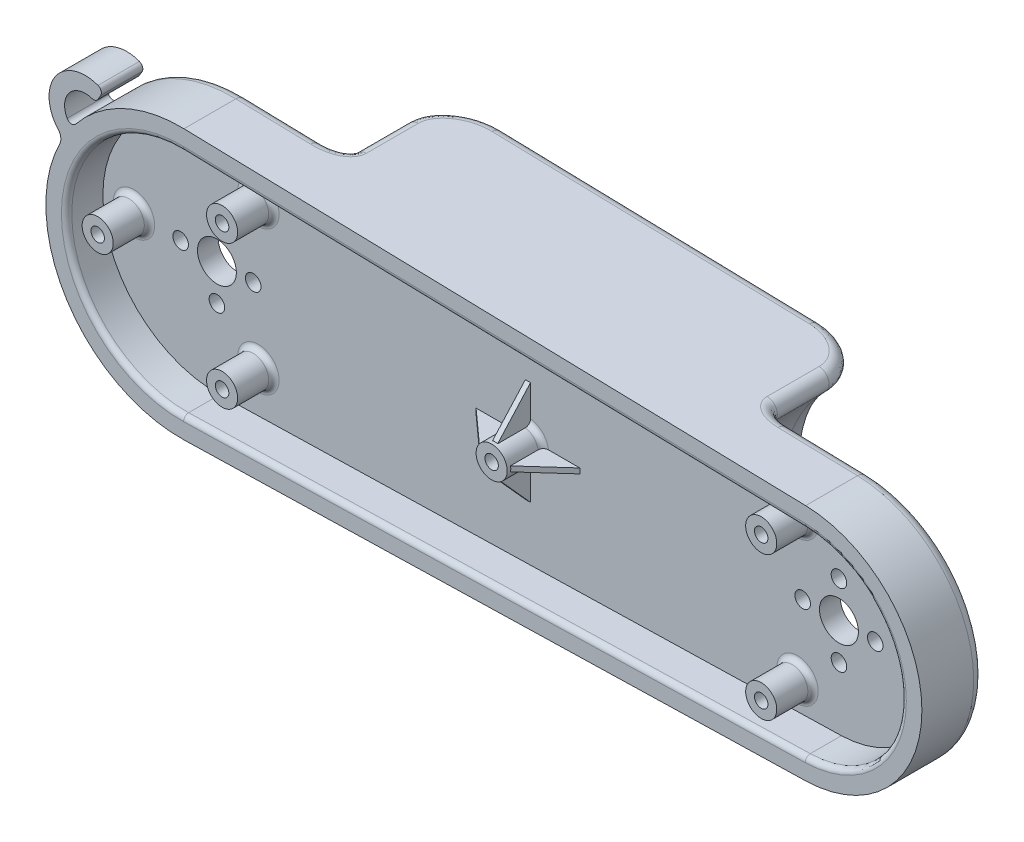
SolidWorks part; units mm, degrees
ref_plane "Front Plane" through (0, 0, 0) normal (0, 0, 1) x (1, 0, 0)
ref_plane "Top Plane" through (0, 0, 0) normal (0, 1, 0) x (1, 0, 0)
ref_plane "Right Plane" through (0, 0, 0) normal (1, 0, 0) x (0, 0, -1)
sketch "Sketch1" plane through (0, 0, 0) normal (0, 0, 1) x (1, 0, 0)
  line L2 (0.65, -25.9919) -> (120.575, -22.9928)
  line L3 (0.65, 25.9919) -> (120.575, 22.9928)
  circle A0 centre (0, 0) radius 3.75
  circle A1 centre (-7, 0) radius 1.5
  circle A2 centre (0, 7) radius 1.5
  circle A3 centre (0, -7) radius 1.5
  circle A4 centre (7, 0) radius 1.5
  arc A5 (0.65, 25.9919) -> (0.65, -25.9919) centre (0, 0) ccw
  circle A6 centre (120, 0) radius 3.75
  circle A7 centre (120, -7) radius 1.5
  circle A8 centre (113, 0) radius 1.5
  circle A9 centre (127, 0) radius 1.5
  circle A10 centre (120, 7) radius 1.5
  arc A11 (120.575, -22.9928) -> (120.575, 22.9928) centre (120, 0) ccw
extrude "Boss-Extrude1" add sketch "Sketch1" along normal blind 12
sketch "Sketch2" plane through (0, 0, 0) normal (0, 0, -1) x (-1, 0, 0)
  circle A0 centre (-120, 0) radius 11
  circle A1 centre (0, 0) radius 11
extrude "Cut-Extrude1" cut sketch "Sketch2" against normal blind 1
sketch "Sketch4" plane through (0, 0, 12) normal (0, 0, 1) x (1, 0, 0)
  line L4 (0.55, -21.9931) -> (120.475, -18.9941)
  line L5 (120.475, 18.9941) -> (0.55, 21.9931)
  line L6 (0.55, -21.9931) -> (120.475, -18.9941)
  line L7 (120.475, 18.9941) -> (0.55, 21.9931)
  arc A4 (0.55, 21.9931) -> (0.55, -21.9931) centre (0, 0) ccw
  arc A5 (120.475, -18.9941) -> (120.475, 18.9941) centre (120, 0) ccw
  arc A6 (0.55, 21.9931) -> (0.55, -21.9931) centre (0, 0) ccw
  arc A7 (120.475, -18.9941) -> (120.475, 18.9941) centre (120, 0) ccw
  dimension "D1" = 4
extrude "Cut-Extrude2" cut sketch "Sketch4" against normal blind 7
sketch "Sketch5" plane through (0, 0, 5) normal (0, 0, 1) x (1, 0, 0)
  line L0 (8, 13.8564) -> (0, 0) construction
  line L1 (-16, 0) -> (0, 0) construction
  line L2 (112, 13.8564) -> (120, 0) construction
  line L3 (120, 0) -> (112, -13.8564) construction
  circle A0 centre (-16, 0) radius 3
  circle A1 centre (8, 13.8564) radius 3
  circle A2 centre (8, -13.8564) radius 3
  circle A3 centre (60, 0) radius 3
  circle A4 centre (112, 13.8564) radius 3
  circle A5 centre (112, -13.8564) radius 3
  dimension "D1" = 6
  dimension "D2" = 16
  dimension "D3" = 60
  dimension "D4" = 120
  dimension "D5" = 120
extrude "Boss-Extrude2" add sketch "Sketch5" along normal up to surface (7 mm away) up to face at (59.5062, 0, 12)
sketch "Sketch6" plane through (0, 0, 12) normal (0, 0, 1) x (1, 0, 0)
  circle A0 centre (8, 13.8564) radius 1.3
  circle A1 centre (60, 0) radius 1.3
  circle A2 centre (-16, 0) radius 1.3
  circle A3 centre (8, -13.8564) radius 1.3
  circle A4 centre (112, -13.8564) radius 1.3
  circle A5 centre (112, 13.8564) radius 1.3
extrude "Cut-Extrude3" cut sketch "Sketch6" against normal blind 8
fillet "Fillet1" radius 1 6 edges at (115, 13.8564, 5) (115, -13.8564, 5) (63, 0, 5) (11, -13.8564, 5) (11, 13.8564, 5) (-13, 0, 5)
fillet "Fillet2" radius 1 4 edges at (139, 0, 12) (-22, 0, 12) (60.5125, -20.4936, 12) (60.5125, 20.4936, 12)
ref_plane "Plane1" through (0, 0, 8) normal (0, 0, -1) x (-1, 0, 0)
sketch "Sketch7" plane through (0, 0, 8) normal (0, 0, -1) x (-1, 0, 0)
  line L0 (0, 0) -> (43.0293, 43.0293) construction
sketch "Sketch9" plane through (0, 0, 0) normal (0, 0, -1) x (-1, 0, 0)
  line L0 (-104.6113, 23.392) -> (-15.612, 25.6177)
  line L1 (-120.575, 22.9928) -> (-0.65, 25.9919) construction
  line L2 (-87.8013, -23.8124) -> (-33.5373, -25.1694)
  line L3 (-33.5373, -25.1694) -> (-29.748, 3.8804)
  line L4 (-0.65, -25.9919) -> (-120.575, -22.9928) construction
  line L5 (-87.8013, -23.8124) -> (-92.3567, 4.4549)
  arc A0 (-92.3567, 4.4549) -> (-104.6113, 23.392) centre (-120, 0) ccw
  arc A1 (-15.612, 25.6177) -> (-29.748, 3.8804) centre (0, 0) ccw
extrude "Boss-Extrude3" add sketch "Sketch9" along normal blind 20
fillet "Fillet3" radius 10 2 edges at (33.5373, -25.1694, -10) (87.8013, -23.8124, -10)
fillet "Fillet4" radius 2 6 edges at (35.7852, -22.5438, 0) (31.0603, -6.1803, 0) (85.8287, -21.5543, 0) (90.7396, -5.5797, 0) (25.1497, 16.3552, 0) (96.4927, 15.212, 0)
fillet "Fillet5" radius 8 7 edges at (25.1497, 16.3552, -20) (31.0603, -6.1803, -20) (35.7852, -22.5438, -20) (61.0192, -24.4822, -20) (85.8287, -21.5543, -20) (90.7396, -5.5797, -20) (96.4927, 15.212, -20)
fillet "Fillet6" radius 2 15 edges at (83.2488, -23.9263, -0.4974) (103.353, -23.4235, 0) (38.7897, -25.0381, -0.4974) (18.2787, -25.551, 0) (-26, 0, 0) (5.8445, 25.862, 0) (15.3352, 25.6246, -1.2721) (15.612, 25.6177, -7) (18.0765, 25.5561, -16.376) (60.6215, 24.4921, -20) (103.296, 23.4249, -15.4259) (104.6113, 23.392, -7) (105.0798, 23.3803, -1.0058) (114.5147, 23.1444, 0) (143, 0, 0)
sketch "Sketch10" plane through (0, 0, 8) normal (0, 0, -1) x (-1, 0, 0)
  line L0 (0, 0) -> (43.0293, 43.0293) construction
  line L1 (16.3848, 21.8489) -> (14.8848, 24.447)
  line L2 (20.2627, 14.853) -> (21.6711, 12.2041)
  arc A0 (22.6232, 12.8138) -> (20.9873, 15.3472) centre (0, 0) ccw
  arc A1 (21.6711, 12.2041) -> (14.8848, 24.447) centre (18.3848, 18.3848) ccw
  arc A2 (20.2627, 14.853) -> (16.3848, 21.8489) centre (18.3848, 18.3848) ccw
  dimension "D1" = 52
  dimension "D2" = 14
  dimension "D3" = 8
  dimension "D4" = 75
  dimension "D5" = 107
extrude "Boss-Extrude4" add sketch "Sketch10" along normal mid plane 8 contours A2 A0 A1 L1 region at (-15.7766, 23.2298, 8)
fillet "Fillet7" radius 2 1 edges at (-22.6232, 12.8138, 8)
fillet "Fillet8" radius 1 3 edges at (-20.9873, 15.3472, 8) (-16.3848, 21.8489, 8) (-14.8848, 24.447, 8)
sketch "Sketch12" plane through (0, 0, 0) normal (0, 1, 0) x (1, 0, 0)
  line L6 (0.55, -5) -> (120.475, -5) construction
  line L7 (50, -5) -> (57.7743, -12)
rib "Rib13" sketch "Sketch12" sketch "Sketch12" thickness 1 extrusion direction parallel to sketch draft on no parameters "D1"=1
pattern_circular "CirPattern1" count 4 over 360 about axis through (60, 0, 4) along (0, 0, 1) of "Rib13" reverse direction yes
